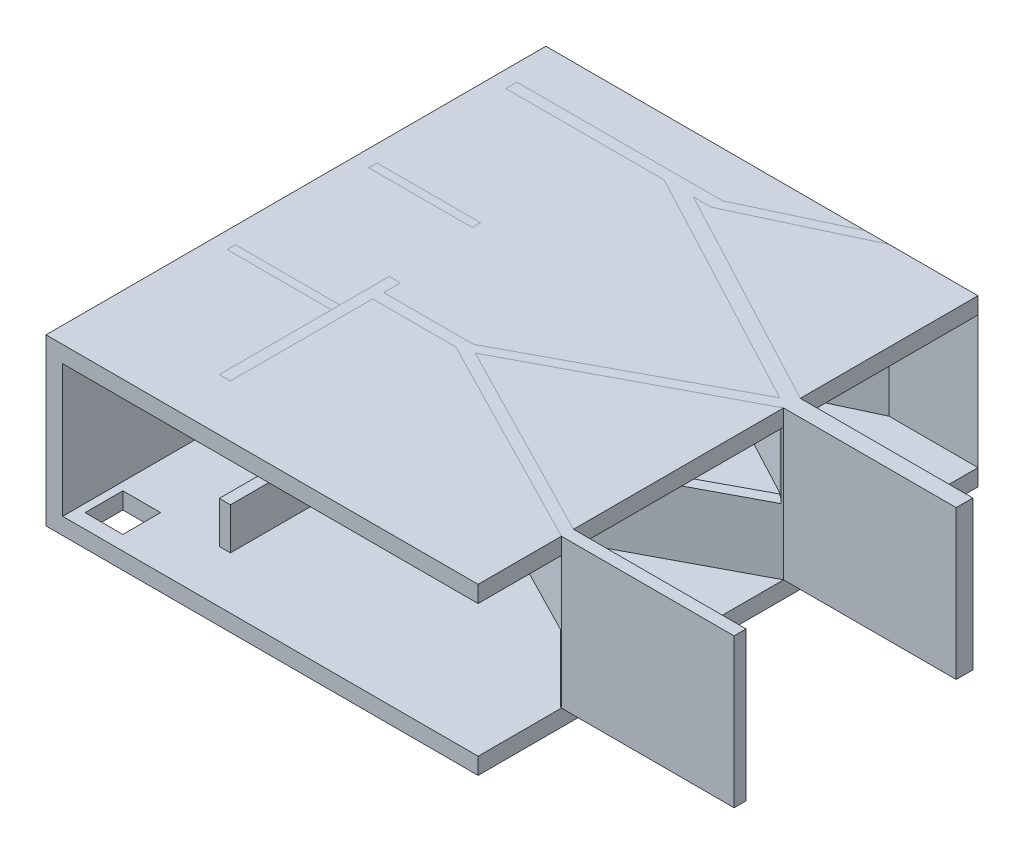
SolidWorks part; units mm, degrees
note: The reader was unsure of these and kept them because the rebuilt part matched: shared geometry of "Sketch4<9>", "Sketch15<2>".
ref_plane "Front Plane" through (0, 0, 0) normal (0, 0, 1) x (1, 0, 0)
ref_plane "Top Plane" through (0, 0, 0) normal (0, 1, 0) x (1, 0, 0)
ref_plane "Right Plane" through (0, 0, 0) normal (1, 0, 0) x (0, 0, -1)
sketch "Sketch1" plane through (0, 0, 0) normal (0, 0, 1) x (1, 0, 0)
  line L0 (5620, 1.7685) -> (5620, 301.7685)
  line L1 (-250, 1.7685) -> (5620, 1.7685)
  line L3 (5620, -2378.2315) -> (50, -2378.2315)
  line L4 (-1860, 1.7685) -> (-1860, -2378.2315)
  line L5 (5620, 301.7685) -> (-2160, 301.7685)
  line L6 (5620, -2678.2315) -> (5620, -2378.2315)
  line L7 (5620, -2678.2315) -> (-2160, -2678.2315)
  line L8 (-2160, 301.7685) -> (-2160, -2678.2315)
  line L10 (50, -2378.2315) -> (-1860, -2378.2315)
  line L11 (-250, 1.7685) -> (-1860, 1.7685)
  dimension "D1" = 7780
  dimension "D2" = 2380
  dimension "D3" = 300
  dimension "D4" = 300
  dimension "D5" = 300
extrude "Boss-Extrude1" add sketch "Sketch1" along normal blind 9000
sketch "Sketch2" plane through (0, 0, 0) normal (0, 0, -1) x (-1, 0, 0)
  line L0 (2160, -2678.2315) -> (-5620, -2678.2315) construction
  line L1 (-5620, 300) -> (2160, 300)
  line L2 (-5620, 300) -> (-5620, -2678.2315)
  line L3 (-5620, -2678.2315) -> (2160, -2678.2315)
  line L4 (2160, 300) -> (2160, -2678.2315)
  line L5 (-5620, -2678.2315) -> (-5620, -2378.2315) construction
extrude "Boss-Extrude2" add sketch "Sketch2" along normal blind 0.1
sketch "Sketch4" plane through (0, -2378.2315, 0) normal (0, 1, 0) x (1, 0, 0)
  line L0 (-1860, -9000) -> (-1860, 0) construction
  line L1 (-1860, -1020) -> (1840, -1020)
  line L2 (-1860, -9000) -> (-1860, 0) construction
  line L3 (-1860, -820) -> (1840, -820)
  line L4 (1840, -1020) -> (1840, -820)
  line L6 (-1860, -820) -> (-1860, -1020)
  line L7 (220, -5500) -> (220, -8060)
  line L8 (1840, -1020) -> (4016.8293, 0)
  line L9 (1840, -820) -> (3590, 0)
  line L10 (4016.8293, 0) -> (3590, 0)
  line L12 (1514.4084, -1020) -> (5620, -3200)
  line L13 (5620, -9000) -> (5620, 0) construction
  line L14 (5428.2889, -3376.6567) -> (990, -1020)
  line L15 (5620, -3500) -> (5620, -3200)
  line L17 (5620, -3500) -> (1837.5479, -5500)
  line L18 (220, -5500) -> (1837.5479, -5500)
  line L20 (1837.5479, -5300) -> (220, -5300)
  line L21 (5620, -7282.7291) -> (1988.271, -5420.304)
  line L22 (5620, -7500) -> (5620, -7282.7291)
  line L23 (5428.2889, -3376.6567) -> (1837.5479, -5300)
  line L24 (20, -5000) -> (20, -5540)
  line L25 (220, -8060) -> (20, -8060)
  line L26 (20, -8060) -> (20, -5540)
  line L27 (220, -5000) -> (220, -5300)
  line L29 (-1036.0133, -8740.4426) -> (-1716.4559, -8740.4426)
  line L30 (-1036.0133, -8740.4426) -> (-1036.0133, -8060)
  line L31 (-1036.0133, -8060) -> (-1716.4559, -8060)
  line L32 (-1716.4559, -8740.4426) -> (-1716.4559, -8060)
  line L33 (5620, -3500) -> (8728.2393, -3500)
  line L34 (1837.5479, -5500) -> (1837.5479, -5300)
  line L35 (5620, -3500) -> (5620, -3200)
  line L36 (5620, -7500) -> (1720, -5500)
  line L37 (5620, -9000) -> (5620, 0) construction
  line L38 (5620, -3200) -> (8728.2393, -3200)
  line L39 (8728.2393, -3500) -> (8728.2393, -3200)
  line L40 (5620, -7500) -> (8728.2393, -7500)
  line L41 (5620, -7500) -> (5620, -7282.7291)
  line L42 (5620, -7282.7291) -> (8728.2393, -7282.7291)
  line L43 (8728.2393, -7500) -> (8728.2393, -7282.7291)
  line L44 (20, -5000) -> (220, -5000)
  line L45 (220, -5000) -> (220, -5500)
  dimension "D2" = 200
  dimension "D3" = 3700
  dimension "D4" = 1750
  dimension "D6" = 850
  dimension "D7" = 2480
  dimension "D8" = 4280
  dimension "D9" = 1880
  dimension "D10" = 2000
  dimension "D11" = 1500
  dimension "D12" = 300
  dimension "D13" = 820
  dimension "D14" = 200
  dimension "D15" = 2560
  dimension "D16" = 200
  dimension "D17" = 300
  dimension "D18" = 4560
extrude "Cut-Extrude1" cut sketch "Sketch4" against normal through all contours L29 L32 L31 L30
extrude "Boss-Extrude3" add sketch "Sketch4<9>" along normal through all
sketch "Sketch4<9>" plane through (0, -2378.2315, 0) normal (0, 1, 0) x (1, 0, 0) same geometry as "Sketch4"
sketch "Sketch11" plane through (0, 1.7685, 0) normal (0, -1, 0) x (1, 0, 0)
  line L0 (4016.8293, 0) -> (5620, 0) construction
  line L1 (5590, 0) -> (1840, 0)
  line L2 (5590, 0) -> (5590, 1150)
  line L3 (5590, 1150) -> (1840, 1150)
  line L4 (1840, 0) -> (1840, 1150)
  line L5 (1837.5479, 5300) -> (1837.5479, 3630)
  line L6 (4743.9766, 3630) -> (1837.5479, 3630)
  line L7 (5590.9608, 3503.5918) -> (5590.9608, 5232.3911)
  line L8 (5590.9608, 5232.3911) -> (3118.3192, 5232.3911)
  line L9 (1837.5479, 5300) -> (1837.5479, 5384.1757)
  line L10 (1988.271, 5420.304) -> (3118.3192, 5420.304)
  line L11 (5590.9608, 3503.5918) -> (5428.2889, 3376.6567)
  line L12 (3118.3192, 5420.304) -> (3118.3192, 5232.3911)
  line L13 (5428.2889, 3376.6567) -> (4743.9766, 3630)
  line L14 (1988.271, 5420.304) -> (1837.5479, 5384.1757)
extrude "Cut-Extrude10" cut sketch "Sketch11" along normal blind 1199
sketch "Sketch13" plane through (0, -2378.2315, 0) normal (0, 1, 0) x (1, 0, 0)
  line L0 (-1860, -1020) -> (990, -1020) construction
  line L1 (357.7758, -1020) -> (5620, -1020)
  line L2 (357.7758, -1020) -> (357.7758, -3389.7259)
  line L3 (5620, -3191.6662) -> (5403.8897, -3389.7259)
  line L4 (5620, -1020) -> (5620, -3191.6662)
  line L9 (5620, -3200) -> (5620, 0) construction
  line L10 (5403.8897, -3389.7259) -> (357.7758, -3389.7259)
  line L11 (5428.2889, -3376.6567) -> (1837.5479, -5300) construction
extrude "Cut-Extrude16" cut sketch "Sketch13" along normal blind 1199
sketch "Sketch14" plane through (0, -2378.2315, 0) normal (0, 1, 0) x (1, 0, 0)
  line L0 (220, -5500) -> (1720, -5500) construction
  line L1 (1347.1888, -5500) -> (1837.5479, -5500)
  line L2 (1347.1888, -5500) -> (1347.1888, -7500)
  line L3 (1347.1888, -7500) -> (5592.4806, -7500)
  line L4 (5592.4806, -5500) -> (5592.4806, -7500)
  line L5 (2143.6782, -5500) -> (1988.271, -5420.304)
  line L6 (5620, -7282.7291) -> (1988.271, -5420.304) construction
  line L7 (1988.271, -5420.304) -> (1837.5479, -5500)
  line L8 (5620, -3500) -> (1988.271, -5420.304) construction
  line L9 (2143.6782, -5500) -> (5592.4806, -5500)
extrude "Cut-Extrude19" cut sketch "Sketch14" along normal blind 1199
sketch "Sketch15" plane through (0, -2378.2315, 0) normal (0, 1, 0) x (1, 0, 0)
  line L0 (2240, -5084.4307) -> (2240, -3490)
  line L1 (5428.2889, -3376.6567) -> (1837.5479, -5300) construction
  line L2 (2240, -3490) -> (-1860, -3490)
  line L3 (-1860, -9000) -> (-1860, -1020) construction
  line L4 (2340, -5030.8667) -> (2340, -3340)
  line L5 (2340, -3340) -> (-1860, -3340)
  line L7 (2240, -5084.4307) -> (2340, -5030.8667)
  line L8 (-1860, -3490) -> (-1860, -3340)
  line L9 (20, -8060) -> (20, -5000) construction
  line L10 (20, -6040) -> (-1860, -6040)
  line L11 (20, -6040) -> (20, -5890)
  line L12 (20, -5890) -> (-1860, -5890)
  line L13 (-1860, -6040) -> (-1860, -5890)
  line L14 (-1860, -9000) -> (-1860, -1020) construction
  line L17 (-1860, -1020) -> (1840, -1020) construction
  line L18 (1837.5479, -5300) -> (220, -5300) construction
  dimension "D1" = 100
  dimension "D2" = 150
  dimension "D3" = 2320
  dimension "D4" = 4100
  dimension "D5" = 150
  dimension "D6" = 2400
  dimension "D7" = 1810
extrude "Boss-Extrude4" add sketch "Sketch15" along normal blind 1140
extrude "Boss-Extrude5" add sketch "Sketch15<2>" along normal through all contours L10 L13 L12 L11
sketch "Sketch15<2>" plane through (0, -2378.2315, 0) normal (0, 1, 0) x (1, 0, 0) same geometry as "Sketch15"
sketch "Sketch16" plane through (0, -1238.2315, 0) normal (0, 1, 0) x (1, 0, 0)
  line L0 (2340, -3340) -> (-1860, -3340) construction
  line L1 (-1860, -3490) -> (2, -3490)
  line L2 (-1860, -3490) -> (-1860, -3340)
  line L3 (-1860, -3340) -> (2, -3340)
  line L4 (2, -3490) -> (2, -3340)
  dimension "D1" = 1862
extrude "Boss-Extrude6" add sketch "Sketch16" along normal through all
sketch "Sketch17" plane through (0, 0, 3490) normal (0, 0, 1) x (1, 0, 0)
  line L0 (2, -1238.2315) -> (2240, -1238.2315) construction
  line L1 (798.9363, -1238.2315) -> (2, -1238.2315)
  line L2 (798.9363, -1238.2315) -> (798.9363, -1188.2315)
  line L3 (798.9363, -1188.2315) -> (2, -1188.2315)
  line L4 (2, -1238.2315) -> (2, -1188.2315)
  line L6 (2, 1.7685) -> (2, -1238.2315) construction
  dimension "D1" = 50
extrude "Boss-Extrude7" add sketch "Sketch17" against normal up to surface (2470 mm away) up to face at (1514.4084, 301.7685, 1020)
sketch "Sketch18" plane through (0, -1188.2315, 0) normal (0, 1, 0) x (1, 0, 0)
  line L0 (84.1309, -3401.5416) -> (723.7267, -3401.5416)
  line L1 (84.1309, -1146.2195) -> (723.7267, -1146.2195)
  line L2 (84.1309, -1146.2195) -> (84.1309, -1349.468)
  line L3 (84.1309, -1349.468) -> (723.7267, -1349.468)
  line L4 (723.7267, -1146.2195) -> (723.7267, -1349.468)
  line L5 (84.1309, -3176.2195) -> (84.1309, -3401.5416)
  line L6 (84.1309, -1639.468) -> (723.7267, -1639.468)
  line L7 (84.1309, -1436.2195) -> (84.1309, -1639.468)
  line L8 (84.1309, -1436.2195) -> (723.7267, -1436.2195)
  line L9 (723.7267, -1436.2195) -> (723.7267, -1639.468)
  line L10 (84.1309, -1929.468) -> (723.7267, -1929.468)
  line L11 (84.1309, -1726.2195) -> (84.1309, -1929.468)
  line L12 (84.1309, -1726.2195) -> (723.7267, -1726.2195)
  line L13 (723.7267, -1726.2195) -> (723.7267, -1929.468)
  line L14 (84.1309, -2219.468) -> (723.7267, -2219.468)
  line L15 (84.1309, -2016.2195) -> (84.1309, -2219.468)
  line L16 (84.1309, -2016.2195) -> (723.7267, -2016.2195)
  line L17 (723.7267, -2016.2195) -> (723.7267, -2219.468)
  line L18 (84.1309, -2509.468) -> (723.7267, -2509.468)
  line L19 (84.1309, -2306.2195) -> (84.1309, -2509.468)
  line L20 (84.1309, -2306.2195) -> (723.7267, -2306.2195)
  line L21 (723.7267, -2306.2195) -> (723.7267, -2509.468)
  line L22 (84.1309, -2799.468) -> (723.7267, -2799.468)
  line L23 (84.1309, -2596.2195) -> (84.1309, -2799.468)
  line L24 (84.1309, -2596.2195) -> (723.7267, -2596.2195)
  line L25 (723.7267, -2596.2195) -> (723.7267, -2799.468)
  line L26 (84.1309, -3089.468) -> (723.7267, -3089.468)
  line L27 (84.1309, -2886.2195) -> (84.1309, -3089.468)
  line L28 (84.1309, -2886.2195) -> (723.7267, -2886.2195)
  line L29 (723.7267, -2886.2195) -> (723.7267, -3089.468)
  line L31 (84.1309, -3176.2195) -> (723.7267, -3176.2195)
  line L32 (723.7267, -3176.2195) -> (723.7267, -3401.5416)
extrude "Cut-Extrude21" cut sketch "Sketch18" against normal blind 100 contours L32 L31 L5 L0 | L10 L13 L12 L11 | L16 L17 L14 L15 | L18 L21 L20 L19 | L22 L25 L24 L23 | L28 L29 L26 L27 | L6 L9 L8 L7 | L3 L4 L1 L2
sketch "Sketch19" plane through (0, 0, 3490) normal (0, 0, 1) x (1, 0, 0)
  line L0 (5620, -2378.2315) -> (-1860, -2378.2315) construction
  line L1 (-210, 21.7685) -> (-135.52, 21.7685)
  line L2 (-210, 21.7685) -> (-210, -52.7115)
  line L3 (-210, -52.7115) -> (-135.52, -52.7115)
  line L4 (-135.52, 21.7685) -> (-135.52, -52.7115)
  line L5 (-135.52, -1123.7315) -> (2.8, -1123.7315)
  line L6 (2.8, -1123.7315) -> (2.8, -1228.2315)
  line L7 (2.8, -1228.2315) -> (-210, -1228.2315)
  line L8 (-210, -1228.2315) -> (-210, -1100.5515)
  line L9 (-210, -1100.5515) -> (-135.52, -1100.5515)
  line L10 (-135.52, -1100.5515) -> (-135.52, -1123.7315)
  line L11 (-1860, -2378.2315) -> (2240, -2378.2315) construction
  line L12 (-1860, 1.7685) -> (-1860, -2378.2315) construction
  dimension "D1" = 1650
  dimension "D2" = 74.48
  dimension "D3" = 74.48
  dimension "D4" = 127.68
  dimension "D5" = 212.8
  dimension "D6" = 104.5
  dimension "D7" = 1150
  dimension "D8" = 2400
extrude "Boss-Extrude8" add sketch "Sketch19" along normal up to surface (1510 mm away) separate body up to face at (120, -1188.2315, 5000)
sketch "Sketch21" plane through (0, -1238.2315, 0) normal (0, 1, 0) x (1, 0, 0)
  line L0 (798.9363, -3490) -> (2240, -3490) construction
  line L1 (810, -3490) -> (2240, -3490)
  line L2 (810, -3490) -> (810, -5300)
  line L3 (2240, -5084.4307) -> (1837.5479, -5300)
  line L4 (2240, -3490) -> (2240, -5084.4307)
  line L5 (2240, -3490) -> (2240, -5084.4307) construction
  line L6 (1837.5479, -5300) -> (810, -5300)
  line L7 (1837.5479, -5300) -> (220, -5300) construction
  dimension "D1" = 1430
extrude "Boss-Extrude9" add sketch "Sketch21" along normal blind 74.48 separate body
sketch "Sketch22" plane through (220, 0, 0) normal (1, 0, 0) x (0, 0, -1)
  line L0 (-8060, 1.7685) -> (-8060, -2378.2315) construction
  line L1 (-8060, -1628.2315) -> (-6040, -1628.2315)
  line L2 (-8060, -1628.2315) -> (-8060, -628.2315)
  line L3 (-8060, -628.2315) -> (-6040, -628.2315)
  line L4 (-6040, -1628.2315) -> (-6040, -628.2315)
  line L5 (-5500, -2378.2315) -> (-8060, -2378.2315) construction
  line L7 (-6040, 1.7685) -> (-6040, -2378.2315) construction
  line L8 (-8060, 1.7685) -> (-5500, 1.7685) construction
  point P6 (-6780, -2378.2315)
  dimension "D1" = 750
  dimension "D2" = 1000
  dimension "D3" = 630
extrude "Cut-Extrude22" cut sketch "Sketch22" against normal blind 597
equation "\"A\"= 4600 + 2850 + 300 + 30"
equation "\"D1@Sketch1\" = \"A\""
equation "\"CUT_stairs\"= 2398 / 2"
equation "\"D1@Cut-Extrude10\"=\"CUT_stairs\""
equation "\"D1@Cut-Extrude19\"=\"CUT_stairs\""
equation "\"D1@Cut-Extrude16\" = \"CUT_stairs\""
equation "\"room_thikn\"=150"
equation "\"D5@Sketch15\"=\"room_thikn\""
equation "\"D2@Sketch15\"=\"room_thikn\""
equation "\"SCALE\"= 106.4"
equation "\"D5@Sketch19\"=\"SCALE\"*2"
equation "\"D4@Sketch19\"=\"SCALE\"*1.2"
equation "\"D2@Sketch19\"=\"SCALE\"*0.7"
equation "\"D3@Sketch19\"=\"SCALE\"*0.7"
